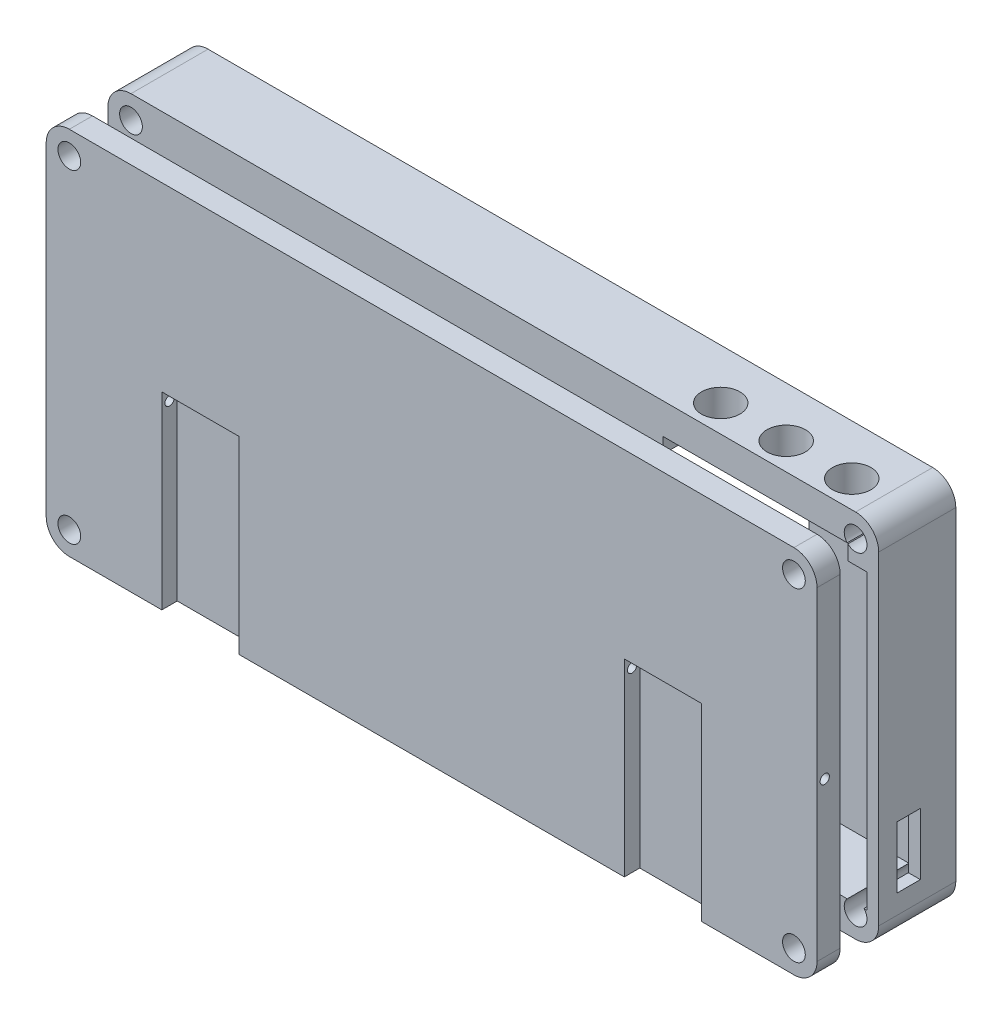
SolidWorks part; units mm, degrees
ref_plane "前视" through (0, 0, 0) normal (0, 0, 1) x (1, 0, 0)
ref_plane "上视" through (0, 0, 0) normal (0, 1, 0) x (1, 0, 0)
ref_plane "右视" through (0, 0, 0) normal (1, 0, 0) x (0, 0, -1)
sketch "草图1" plane through (0, 0, 0) normal (1, 0, 0) x (0, 0, -1)
  line L0 (0, 0) -> (10, 0)
  line L1 (0, 48) -> (0, 0)
  line L2 (10, 0) -> (10, 48)
  line L3 (10, 48) -> (0, 48)
  dimension "D1" = 10
  dimension "D2" = 48
extrude "凸台-拉伸2" add sketch "草图1" along normal blind 100 contours L1 L0 L2 L3
sketch "草图4" plane through (0, 0, 0) normal (0, 0, 1) x (1, 0, 0)
  line L0 (50, 0) -> (50, 46) construction
  line L1 (100, 0) -> (0, 0) construction
  line L2 (100, 48) -> (0, 48) construction
  line L3 (100, 48) -> (100, 0) construction
  line L4 (1.55, 42) -> (98.45, 42)
  line L5 (1.55, 42) -> (1.55, 4)
  line L6 (1.55, 4) -> (98.45, 4)
  line L7 (98.45, 42) -> (98.45, 4)
  line L8 (1.55, 42) -> (98.45, 4) construction
  line L9 (1.55, 4) -> (98.45, 42) construction
  line L10 (81.945, 37.525) -> (82.945, 36.525)
  line L11 (18.055, 37.525) -> (81.945, 37.525)
  line L12 (17.055, 36.525) -> (17.055, 10.475)
  line L13 (18.055, 9.475) -> (81.945, 9.475)
  line L14 (82.945, 36.525) -> (82.945, 10.475)
  line L15 (17.055, 37.525) -> (82.945, 9.475) construction
  line L16 (17.055, 9.475) -> (82.945, 37.525) construction
  line L17 (17.055, 36.525) -> (18.055, 37.525)
  line L18 (17.055, 10.475) -> (18.055, 9.475)
  line L19 (81.945, 9.475) -> (82.945, 10.475)
  point P6 (50, 23)
  point P13 (50, 23.5)
  dimension "D2" = 38
  dimension "D3" = 96.9
  dimension "D4" = 1.55
  dimension "D6" = 65.89
  dimension "D7" = 28.05
  dimension "D8" = 2
extrude "切除-拉伸3" cut sketch "草图4" against normal through all contours L14 L11 L12 L13 region at (50, 23.5, 0)
extrude "切除-拉伸4" cut sketch "草图4<3>" against normal offset from surface (8 mm away) 2 contours L7 L4 L5 L6 L11 L14 L13 L12 region at (50, 40.9592, 0) up to face at (50, 23.5, -10)
sketch "草图4<3>" plane through (0, 0, 0) normal (0, 0, 1) x (1, 0, 0) same geometry as "草图4"
chamfer "倒角4" distance 2 angle 60 8 edges at (17.055, 23.5, -10) (17.555, 37.025, -10) (50, 37.525, -10) (82.445, 37.025, -10) (82.945, 23.5, -10) (82.445, 9.975, -10) (50, 9.475, -10) (17.555, 9.975, -10) first distance on face at (17.055, 23.5, -9) first distance on face at (17.555, 37.025, -9) first distance on face at (50, 37.525, -9) first distance on face at (82.445, 37.025, -9) first distance on face at (82.945, 23.5, -9) first distance on face at (82.445, 9.975, -9) first distance on face at (50, 9.475, -9) first distance on face at (17.555, 9.975, -9)
fillet "圆角1" radius 3 4 edges at (0, 0, -5) (100, 0, -5) (0, 48, -5) (100, 48, -5)
sketch "草图13" plane through (0, 0, 0) normal (0, 0, 1) x (1, 0, 0)
  line L0 (1.55, 42) -> (98.45, 42) construction
  line L1 (96, 42) -> (72, 42)
  line L2 (96, 42) -> (96, 44)
  line L3 (96, 44) -> (72, 44)
  line L4 (72, 42) -> (72, 44)
  line L5 (100, 45) -> (100, 3) construction
  dimension "D1" = 4
  dimension "D2" = 28
  dimension "D3" = 2
extrude "切除-拉伸17" cut sketch "草图13" against normal up to surface (8 mm away) up to face at (50, 23, -8)
sketch "草图12" plane through (0, 48, 0) normal (0, 1, 0) x (1, 0, 0)
  line L1 (97, 10) -> (3, 10) construction
  line L9 (100, 10) -> (100, 0) construction
  circle A0 centre (76, 3.5) radius 2.5
  circle A1 centre (93, 3.5) radius 2.5
  circle A2 centre (84.5, 3.5) radius 2.5
  point P2 (0, 0)
  point P3 (71.8731, 3.5)
  dimension "D1" = 5
  dimension "D2" = 24
  dimension "D6" = 7
  dimension "D4" = 5
  dimension "D5" = 5
  dimension "D7" = 15.5
  dimension "D8" = 6.5
extrude "切除-拉伸18" cut sketch "草图12" against normal up to next
sketch "草图15" plane through (0, 0, 0) normal (0, -1, 0) x (1, 0, 0)
  line L1 (67.5, -7) -> (72.5, -7)
  line L2 (67.5, -7) -> (67.5, -3)
  line L3 (67.5, -3) -> (72.5, -3)
  line L4 (72.5, -7) -> (72.5, -3)
  line L5 (100, 0) -> (100, -10) construction
  line L6 (97, -5) -> (89.4882, -5) construction
  line L7 (97, -10) -> (97, 0) construction
  arc A0 (67.5, -3) -> (67.5, -7) centre (67.5, -5) ccw
  arc A1 (72.5, -3) -> (72.5, -7) centre (72.5, -5) cw
  point P4 (0, 0)
  point P6 (0, 0)
  point P16 (0, 0)
  point P17 (0, 0)
  dimension "D1" = 27.5
  dimension "D2" = 32.5
  dimension "D3" = 4
sketch "草图14" plane through (100, 0, 0) normal (1, 0, 0) x (0, 0, -1)
  line L0 (10, 0) -> (0, 0) construction
  line L1 (2.4, 5.5) -> (5.4, 5.5)
  line L2 (2.4, 5.5) -> (2.4, 13.5)
  line L3 (2.4, 13.5) -> (5.4, 13.5)
  line L4 (5.4, 5.5) -> (5.4, 13.5)
  line L5 (8, 4) -> (8, 42) construction
  point P6 (3.9, 5.5)
  point P9 (8, 23)
  dimension "D1" = 8
  dimension "D2" = 3
  dimension "D3" = 5.5
  dimension "D4" = 2.6
extrude "切除-拉伸19" cut sketch "草图14" against normal up to next
extrude "切除-拉伸20" cut sketch "草图15" against normal up to next contours L1 L4 L3 L2 | A1 L4 | L2 A0 region at (70, 0, -5) region at (66.6512, 0, -5) region at (73.3488, 0, -5)
sketch "草图16" plane through (0, 0, 0) normal (0, 0, 1) x (1, 0, 0)
  line L0 (1.55, 4) -> (98.45, 4) construction
  line L1 (62.5, 4) -> (77.5, 4)
  line L2 (62.5, 4) -> (62.5, 2)
  line L3 (62.5, 2) -> (77.5, 2)
  line L4 (77.5, 4) -> (77.5, 2)
  line L8 (74.5, 0) -> (74.5, 4) construction
  line L9 (65.5, 4) -> (65.5, 0) construction
  dimension "D1" = 2
  dimension "D2" = 3
  dimension "D3" = 3
extrude "切除-拉伸21" cut sketch "草图16" against normal up to surface (8 mm away) up to face at (67, 33, -8)
sketch "草图7" plane through (0, 0, 0) normal (0, 0, 1) x (1, 0, 0)
  line L4 (0, 45) -> (0, 3)
  line L5 (3, 0) -> (97, 0)
  line L6 (100, 3) -> (100, 45)
  line L7 (97, 48) -> (3, 48)
  line L8 (0, 45) -> (0, 3)
  line L9 (3, 0) -> (97, 0)
  line L10 (100, 3) -> (100, 45)
  line L11 (97, 48) -> (3, 48)
  arc A4 (0, 3) -> (3, 0) centre (3, 3) ccw
  arc A5 (97, 0) -> (100, 3) centre (97, 3) ccw
  arc A6 (100, 45) -> (97, 48) centre (97, 45) ccw
  arc A7 (3, 48) -> (0, 45) centre (3, 45) ccw
  arc A8 (0, 3) -> (3, 0) centre (3, 3) ccw
  arc A9 (97, 0) -> (100, 3) centre (97, 3) ccw
  arc A10 (100, 45) -> (97, 48) centre (97, 45) ccw
  arc A11 (3, 48) -> (0, 45) centre (3, 45) ccw
  dimension "D1" = 0
extrude "凸台-拉伸3" add sketch "草图7" along normal blind 3 from offset 5 separate body
sketch "草图8" plane through (0, 0, 8) normal (0, 0, 1) x (1, 0, 0)
  line L0 (50, 48) -> (50, 0) construction
  line L1 (3, 0) -> (97, 0)
  line L2 (15, 0) -> (15, 24)
  line L3 (75, 0) -> (85, 0)
  line L4 (0, 45) -> (0, 3)
  line L5 (3, 0) -> (97, 0)
  line L6 (100, 3) -> (100, 45)
  line L7 (97, 48) -> (3, 48)
  line L8 (0, 45) -> (0, 3)
  line L9 (75, 0) -> (75, 24)
  line L10 (100, 3) -> (100, 45)
  line L11 (97, 48) -> (3, 48)
  line L12 (75, 24) -> (85, 24)
  line L13 (85, 0) -> (85, 24)
  line L14 (25, 0) -> (25, 24)
  line L15 (25, 24) -> (15, 24)
  line L17 (15, 24) -> (25, 24)
  line L18 (15, 24) -> (15, 24.5)
  line L19 (15, 24.5) -> (25, 24.5)
  line L20 (25, 24) -> (25, 24.5)
  line L21 (75, 24) -> (85, 24)
  line L22 (75, 24) -> (75, 24.5)
  line L23 (75, 24.5) -> (85, 24.5)
  line L24 (85, 24) -> (85, 24.5)
  arc A4 (3, 48) -> (0, 45) centre (3, 45) ccw
  arc A5 (0, 3) -> (3, 0) centre (3, 3) ccw
  arc A6 (97, 0) -> (100, 3) centre (97, 3) ccw
  arc A7 (100, 45) -> (97, 48) centre (97, 45) ccw
  arc A8 (3, 48) -> (0, 45) centre (3, 45) ccw
  arc A9 (0, 3) -> (3, 0) centre (3, 3) ccw
  arc A10 (97, 0) -> (100, 3) centre (97, 3) ccw
  arc A11 (100, 45) -> (97, 48) centre (97, 45) ccw
  line M13 (3, 0) -> (97, 0)
  dimension "D2" = 10
  dimension "D3" = 24
  dimension "D4" = 50
  dimension "D5" = 0.5
  dimension "D6" = 0.5
  dimension "D1" = 0
extrude "切除-拉伸9" cut sketch "草图8" against normal blind 2 contours L14 L15 L2 L1 | L13 L12 L9 M13 region at (20, 12, 8) region at (80, 12, 8)
sketch "草图9" plane through (75, 0, 0) normal (1, 0, 0) x (0, 0, -1)
  line L0 (-6, 24) -> (-8, 24) construction
  line L1 (-7, 24) -> (-7, 22.9259) construction
  circle A0 centre (-7, 23) radius 0.6
  dimension "D1" = 1
extrude "切除-拉伸10" cut sketch "草图9" against normal through all both and the other way through all
sketch "草图10" plane through (0, 0, 8) normal (0, 0, 1) x (1, 0, 0)
  line L0 (0, 24) -> (78.5549, 24) construction
  line L1 (0, 45) -> (0, 3) construction
  line L2 (50, 48) -> (50, 3.3947) construction
  line L3 (97, 48) -> (3, 48) construction
  circle A0 centre (3, 45) radius 1.475
  arc A1 (3, 48) -> (0, 45) centre (3, 45) ccw construction
  circle A3 centre (97, 45) radius 1.475
  circle A4 centre (97, 3) radius 1.475
  circle A5 centre (3, 3) radius 1.475
  dimension "D1" = 2.95
extrude "切除-拉伸12" cut sketch "草图10" against normal through all
extrude "切除-拉伸16" cut sketch "草图8<4>" against normal blind 1 contours L15 L20 L19 L18 | L12 L24 L23 L22 region at (20, 24.25, 8) region at (80, 24.25, 8)
sketch "草图8<4>" plane through (0, 0, 8) normal (0, 0, 1) x (1, 0, 0) same geometry as "草图8"
